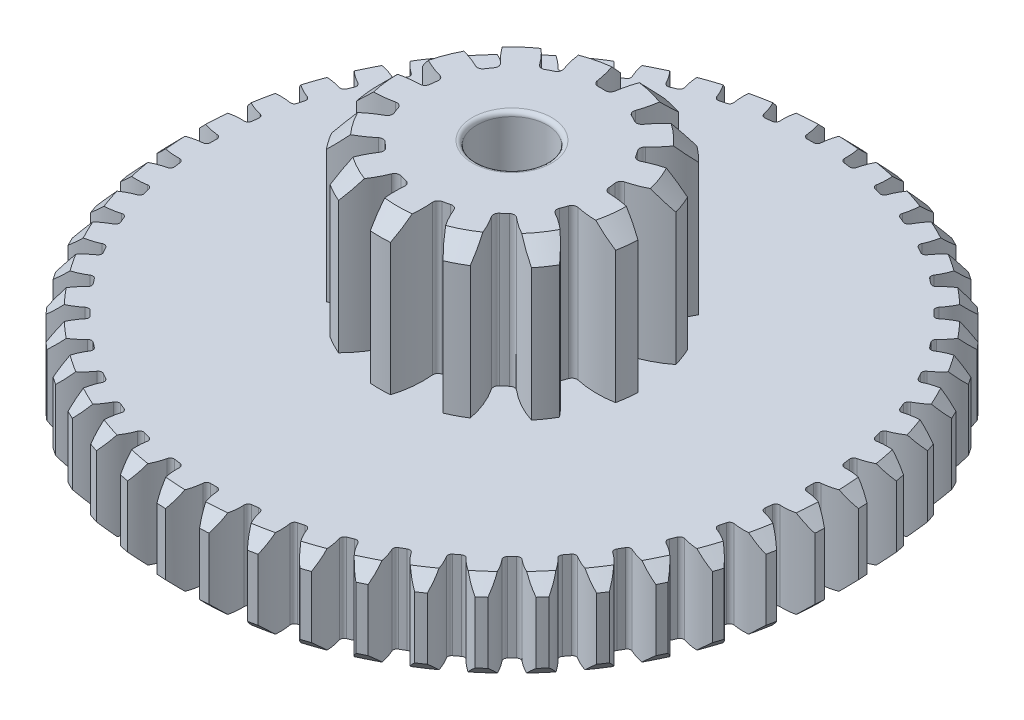
SolidWorks part; units mm, degrees
ref_plane "Front Plane" through (0, 0, 0) normal (0, 0, 1) x (1, 0, 0)
ref_plane "Top Plane" through (0, 0, 0) normal (0, 1, 0) x (1, 0, 0)
ref_plane "Right Plane" through (0, 0, 0) normal (1, 0, 0) x (0, 0, -1)
sketch "Sketch2" plane through (0, 0, 0) normal (0, 1, 0) x (1, 0, 0)
  circle A0 centre (0, 0) radius 2.6 construction
  circle A1 centre (0, 0) radius 3
  dimension "D1" = 5.2
  dimension "D2" = 6
extrude "Boss-Extrude1" add sketch "Sketch2" along normal blind 3.4
sketch "Sketch3" plane through (0, 3.4, 0) normal (0, 1, 0) x (1, 0, 0)
  line L0 (0, 0) -> (0, 3) construction
  line L1 (0, 0) -> (1.3942, 2.6564) construction
  line L2 (0, 0) -> (0.7179, 2.9128) construction
  line L3 (-0.1898, 2.0312) -> (0, 0) construction
  line L4 (-0.3134, 2.581) -> (0.3134, 2.581) construction
  line L5 (0.3134, 2.581) -> (0.922, 2.431) construction
  line L6 (-0.4533, 2.9655) -> (0, 1.72) construction
  circle A0 centre (0, 0) radius 2.2 construction
  circle A2 centre (0, 0) radius 3 construction
  arc A3 (-0.4933, 2.9592) -> (-0.1898, 2.0312) centre (-2.3887, 1.8257) cw
  circle A4 centre (0, 0) radius 3 construction
  arc A5 (0.4933, 2.9592) -> (0.1898, 2.0312) centre (2.3887, 1.8257) ccw
  circle A6 centre (0, 0) radius 2.6 construction
  arc A7 (0.4933, 2.9592) -> (-0.4933, 2.9592) centre (0, 0) ccw
  arc A8 (0.1898, 2.0312) -> (-0.1898, 2.0312) centre (0, 0) ccw
  dimension "D1" = 27.692
  dimension "D2" = 0.8
  dimension "D4" = 20
extrude "Cut-Extrude1" cut sketch "Sketch3" against normal through all
fillet "Fillet1" radius 0.12 2 edges at (-0.1898, 1.7, -2.0312) (0.1898, 1.7, -2.0312)
chamfer "Chamfer1" distance 0.4 1 edges at (0, 3.4, 3)
pattern_circular "CirPattern1" count 13 over 360 about axis through (0, 3.4, 0) along (0, -1, 0) of "Fillet1", "Cut-Extrude1"
sketch "Sketch4" plane through (0, 0, 0) normal (0, -1, 0) x (1, 0, 0)
  circle A0 centre (0, 0) radius 7.2 construction
  circle A1 centre (0, 0) radius 7.5
  dimension "D1" = 14.4
  dimension "D2" = 15
extrude "Boss-Extrude3" add sketch "Sketch4" along normal blind 2
sketch "Sketch7" plane through (0, -2, 0) normal (0, -1, 0) x (1, 0, 0)
  line L0 (0, 7.5) -> (0, 0) construction
  line L1 (0, 0) -> (0.9789, 7.4358) construction
  line L2 (0, 0) -> (0.4905, 7.4839) construction
  line L3 (-0.1569, 6.7782) -> (0, 0) construction
  line L4 (-0.2356, 7.1961) -> (0.2356, 7.1961) construction
  line L5 (0.2356, 7.1961) -> (0.7057, 7.1653) construction
  line L6 (-0.3433, 7.4921) -> (0, 6.5489) construction
  arc A0 (0.9006, 6.841) -> (-0.1652, 6.898) centre (0, 0) ccw construction
  circle A2 centre (0, 0) radius 7.5 construction
  arc A3 (-0.1569, 6.7782) -> (-0.3869, 7.49) centre (-1.4672, 6.7479) ccw
  arc A4 (0.1569, 6.7782) -> (0.3869, 7.49) centre (1.4672, 6.7479) cw
  circle A5 centre (0, 0) radius 7.2 construction
  arc A6 (0.3869, 7.49) -> (-0.3869, 7.49) centre (0, 0) ccw
  arc A7 (0.1569, 6.7782) -> (-0.1569, 6.7782) centre (0, 0) ccw
  dimension "D4" = 20
  dimension "D1" = 7.5
extrude "Cut-Extrude2" cut sketch "Sketch7" against normal up to next
fillet "Fillet2" radius 0.09 2 edges at (0.1569, -1, 6.7782) (-0.1569, -1, 6.7782)
chamfer "Chamfer2" distance 0.3 2 edges at (0, 0, -7.5) (0, -2, -7.5)
pattern_circular "CirPattern2" count 48 over 360 about axis through (0, -2, 0) along (0, 1, 0) of "Fillet2", "Cut-Extrude2"
sketch "Sketch8" plane through (0, 3.4, 0) normal (0, 1, 0) x (1, 0, 0)
  circle A0 centre (0, 0) radius 0.8
  dimension "D1" = 1.6
extrude "Cut-Extrude3" cut sketch "Sketch8" against normal through all
fillet "Fillet3" radius 0.1 1 edges at (0, 3.4, 0.8)
equation "\"Module of small gear\"= 0.4mm"
equation "\"Number of teeth of small gear\"= 13"
equation "\"Pressure Angle\"= 20"
equation "\"D1@Sketch2\"=\"Module of small gear\" * \"Number of teeth of small gear\""
equation "\"D2@Sketch2\"=(\"Number of teeth of small gear\" + 2) * \"Module of small gear\""
equation "\"D1@Sketch3\"=360 / \"Number of teeth of small gear\""
equation "\"D2@Sketch3\"=\"Module of small gear\" * 2"
equation "\"D4@Sketch3\"=\"Pressure Angle\""
equation "\"D1@Fillet1\"=0.3 * \"Module of small gear\""
equation "\"D1@CirPattern1\"=\"Number of teeth of small gear\""
equation "\"D1@Chamfer1\"=\"Module of small gear\""
equation "\"Module of big gear\"= 0.3mm"
equation "\"Number of teeth of big gear\"= 48"
equation "\"D1@Sketch4\"=\"Module of big gear\" * \"Number of teeth of big gear\""
equation "\"D2@Sketch4\"=(\"Number of teeth of big gear\" + 2) * \"Module of big gear\""
equation "\"D1@Sketch7\"=360 / \"Number of teeth of big gear\""
equation "\"D2@Sketch7\"=\"Module of big gear\" * 2"
equation "\"D4@Sketch7\"=\"Pressure Angle\""
equation "\"D1@Fillet2\"=0.3 * \"Module of big gear\""
equation "\"D1@CirPattern2\"=\"Number of teeth of big gear\""
